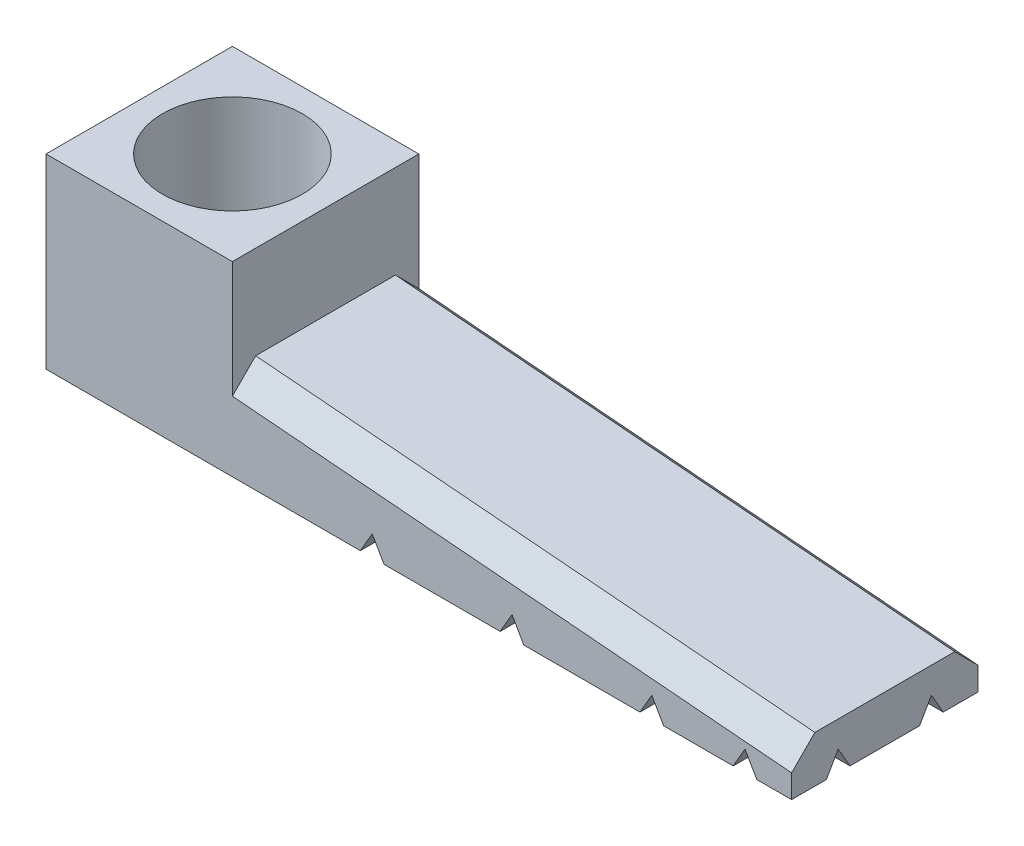
SolidWorks part; units mm, degrees
ref_plane "Front Plane" through (0, 0, 0) normal (0, 0, 1) x (1, 0, 0)
ref_plane "Top Plane" through (0, 0, 0) normal (0, 1, 0) x (1, 0, 0)
ref_plane "Right Plane" through (0, 0, 0) normal (1, 0, 0) x (0, 0, -1)
sketch "Sketch1" plane through (0, 0, 0) normal (0, 0, 1) x (1, 0, 0)
  line L0 (0, 0) -> (0, 20)
  line L1 (0, 20) -> (20, 20)
  line L2 (20, 20) -> (20, 10)
  line L3 (0, 0) -> (80, 0)
  line L4 (80, 0) -> (80, 5)
  line L5 (80, 5) -> (20, 10)
  dimension "D1" = 20
  dimension "D2" = 20
  dimension "D3" = 10
  dimension "D4" = 80
  dimension "D5" = 5
extrude "Boss-Extrude1" add sketch "Sketch1" along normal blind 20
chamfer "Chamfer1" distance 2.5 angle 45 2 edges at (50, 7.5, 0) (50, 7.5, 20)
ref_plane "Plane1" through (0, 0, 0) normal (0, -1, 0) x (-1, 0, 0)
sketch "Sketch2" plane through (0, 0, 0) normal (0, -1, 0) x (-1, 0, 0)
  line L0 (0, -10) -> (-20, -10) construction
  line L1 (0, -20) -> (0, 0) construction
  line L2 (-10, -1010) -> (-10, 48990) construction
  circle A0 centre (-10, -10) radius 7.5
  point P7 (-10, -10)
  dimension "D1" = 15
extrude "Cut-Extrude1" cut sketch "Sketch2" against normal through all
ref_plane "Plane2" through (80, 0, 0) normal (1, 0, 0) x (0, 0, -1)
sketch "Sketch3" plane through (80, 0, 0) normal (1, 0, 0) x (0, 0, -1)
  line L0 (-15, -997.6224) -> (-15, 49002.3776) construction
  line L2 (-5, -998.5989) -> (-5, 49001.4011) construction
  line L3 (0, 0) -> (0, 2.4913) construction
  line L4 (-20, 20) -> (-20, 0) construction
  line L5 (-20, 0) -> (0, 0) construction
  line L6 (-15, 2.1997) -> (-16.27, 0)
  line L7 (-16.27, 0) -> (-13.73, 0)
  line L8 (-13.73, 0) -> (-15, 2.1997)
  line L9 (-10, -995) -> (-10, 49005) construction
  line L10 (-20, 0) -> (-20, 2.4913) construction
  line L11 (-6.27, 0) -> (-5, 2.1997)
  line L12 (-3.73, 0) -> (-6.27, 0)
  line L13 (-5, 2.1997) -> (-3.73, 0)
  circle A0 centre (-15, 0.7332) radius 0.7332 construction
  circle A1 centre (-5, 0.7332) radius 0.7332 construction
  dimension "D3" = 2.54
  dimension "D1" = 5
  dimension "D2" = 5
  dimension "D4" = 10
extrude "Cut-Extrude2" cut sketch "Sketch3" against normal up to surface (60 mm away) up to face at (20, 12.4971, 10)
sketch "Sketch4" plane through (0, 0, 0) normal (0, 0, 1) x (1, 0, 0)
  line L0 (0, 0) -> (80, 0) construction
  line L1 (75, 2.1997) -> (73.73, 0)
  line L2 (73.73, 0) -> (76.27, 0)
  line L3 (76.27, 0) -> (75, 2.1997)
  line L4 (80, 0) -> (80, 2.4913) construction
  line L5 (65, 2.1997) -> (63.73, 0)
  line L6 (63.73, 0) -> (66.27, 0)
  line L7 (66.27, 0) -> (65, 2.1997)
  line L9 (50, 2.1997) -> (48.73, 0)
  line L10 (48.73, 0) -> (51.27, 0)
  line L11 (51.27, 0) -> (50, 2.1997)
  line L12 (35, 2.1997) -> (33.73, 0)
  line L13 (33.73, 0) -> (36.27, 0)
  line L14 (36.27, 0) -> (35, 2.1997)
  circle A0 centre (75, 0.7332) radius 0.7332 construction
  circle A1 centre (65, 0.7332) radius 0.7332 construction
  circle A2 centre (50, 0.7332) radius 0.7332 construction
  circle A3 centre (35, 0.7332) radius 0.7332 construction
  dimension "D1" = 2.54
  dimension "D2" = 5
  dimension "D3" = 2.54
  dimension "D4" = 15
  dimension "D5" = 2.54
  dimension "D6" = 2.54
  dimension "D7" = 30
  dimension "D8" = 45
extrude "Cut-Extrude3" cut sketch "Sketch4" along normal through all
